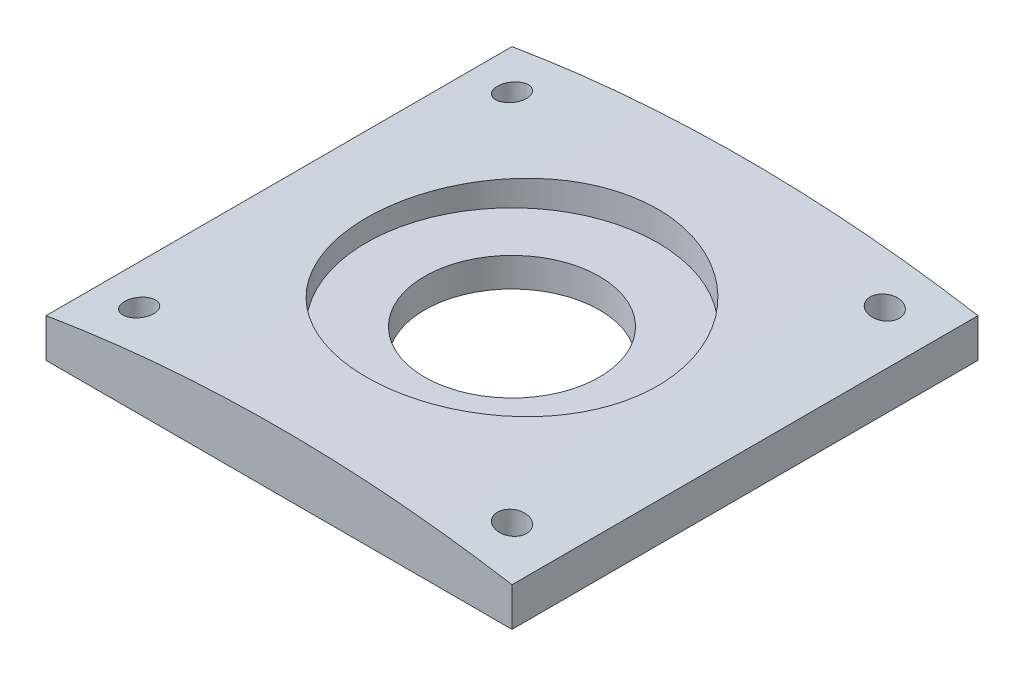
SolidWorks part; units mm, degrees
ref_plane "Front Plane" through (0, 0, 0) normal (0, 0, 1) x (1, 0, 0)
ref_plane "Top Plane" through (0, 0, 0) normal (0, 1, 0) x (1, 0, 0)
ref_plane "Right Plane" through (0, 0, 0) normal (1, 0, 0) x (0, 0, -1)
sketch "Sketch1" plane through (0, 0, 0) normal (0, 1, 0) x (1, 0, 0)
  line L1 (-40, -40) -> (40, -40)
  line L2 (-40, -40) -> (-40, 40)
  line L3 (-40, 40) -> (40, 40)
  line L4 (40, -40) -> (40, 40)
  line L5 (-40, -40) -> (40, 40) construction
  line L6 (-40, 40) -> (40, -40) construction
  circle A0 centre (0, 0) radius 15
  circle A1 centre (0, 0) radius 25
  circle A2 centre (-32, 32) radius 2.5
  circle A3 centre (-32, -32) radius 2.5
  circle A4 centre (32, -32) radius 2.5
  circle A5 centre (32, 32) radius 2.5
  point P19 (0, 0)
  dimension "D1" = 50
  dimension "D2" = 30
  dimension "D4" = 5
  dimension "D3" = 80
  dimension "D5" = 8
  dimension "D6" = 4
extrude "Boss-Extrude3" add sketch "Sketch1<3>" against normal blind 5 contours L1 L4 L3 L2 A1 | A1 A0 region at (-38.8686, 0, 0) region at (-24.2929, 0, 0)
sketch "Sketch1<3>" plane through (0, 0, 0) normal (0, 1, 0) x (1, 0, 0) same geometry as "Sketch1"
extrude "Boss-Extrude4" add sketch "Sketch1" along normal blind 5 contours L1 L4 L3 L2 A1 region at (-38.8686, 0, 0)
sketch "Sketch3" plane through (0, 0, 0) normal (0, 0, 1) x (1, 0, 0)
  line L0 (0, 5) -> (0, -235) construction
  line L1 (-40, 5) -> (40, 5) construction
  line L2 (40, -5) -> (40, 5) construction
  line L3 (-40, -5) -> (-40, 5) construction
  line L4 (-40, 1.6432) -> (-40, 5)
  line L5 (-40, 5) -> (0, 5)
  line L6 (40, 5) -> (40, 1.6432)
  line L7 (0, 5) -> (40, 5)
  arc A0 (0, 5) -> (40, 1.6432) centre (0, -235) cw
  arc A1 (0, 5) -> (-40, 1.6432) centre (0, -235) ccw
  dimension "D1" = 240
extrude "Cut-Extrude2" cut sketch "Sketch3" against normal through all both and the other way through all contours A1 L4 L5
extrude "Cut-Extrude3" cut sketch "Sketch3<4>" against normal through all both and the other way through all contours L7 L6 A0
sketch "Sketch3<4>" plane through (0, 0, 0) normal (0, 0, 1) x (1, 0, 0) same geometry as "Sketch3"
